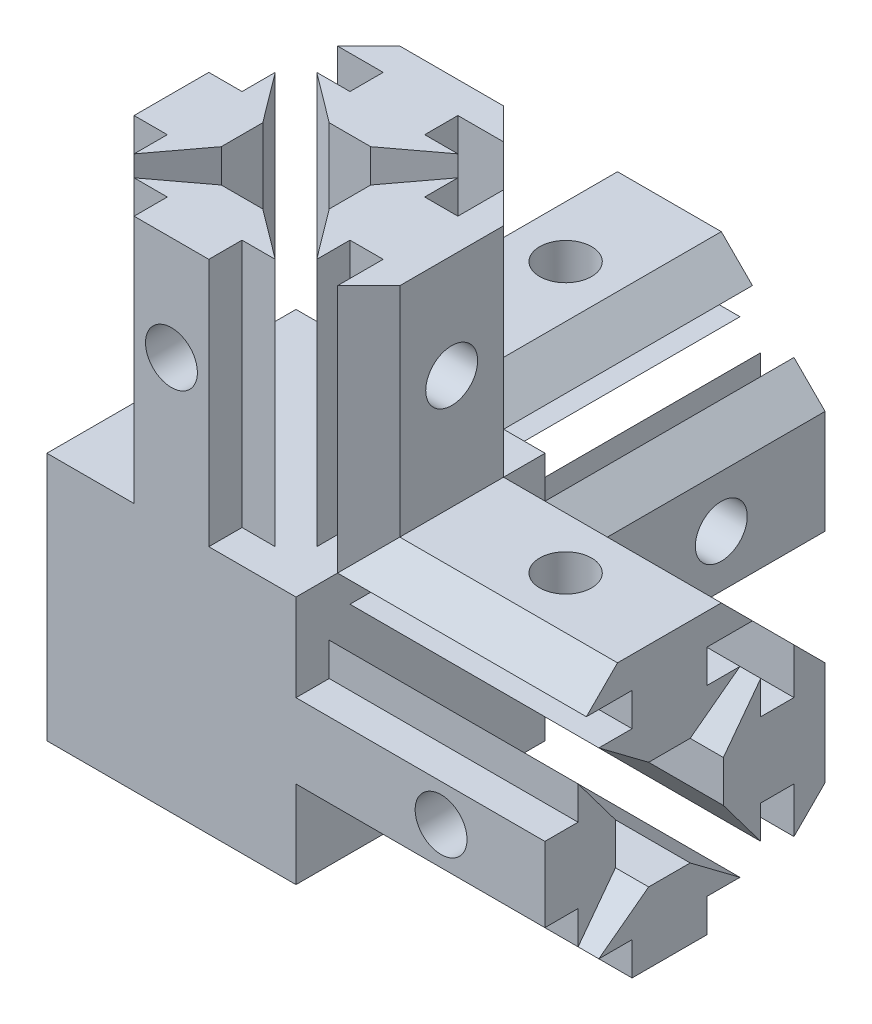
SolidWorks part; units mm, degrees
ref_plane "Plan de face" through (0, 0, 0) normal (0, 0, 1) x (1, 0, 0)
ref_plane "Plan de dessus" through (0, 0, 0) normal (0, 1, 0) x (1, 0, 0)
ref_plane "Plan de droite" through (0, 0, 0) normal (1, 0, 0) x (0, 0, -1)
ref_axis "Axe1" through (0, 17.691, 0) along (0, -1, 0)
ref_axis "Axe2" through (11.6947, 0, 0) along (-1, 0, 0)
ref_axis "Axe3" through (0, 0, -21.7718) along (0, 0, 1)
sketch "Esquisse1" plane through (0, 0, 0) normal (0, 0, 1) x (1, 0, 0)
  line L1 (-6, 6) -> (6, 6)
  line L2 (-6, 6) -> (-6, -6)
  line L3 (-6, -6) -> (6, -6)
  line L4 (6, 6) -> (6, -6)
  point P4 (0, 6)
  point P5 (-6, 0)
  dimension "D1" = 12
  dimension "D2" = 12
extrude "Boss.-Extru.1" add sketch "Esquisse1" along normal mid plane 12
ref_plane "Plan Construction" through (0, 5.99, 0) normal (0, 1, 0) x (1, 0, 0)
sketch "Esquisse8" plane through (0, 5.99, 0) normal (0, 1, 0) x (1, 0, 0)
  line L0 (-6, 1.8) -> (-4.4, 1.8)
  line L2 (-4.4, 1.8) -> (-4.4, 3.4)
  line L3 (-4.4, 3.4) -> (-2.6, 1)
  line L4 (-2.6, 1) -> (-2.6, -1)
  line L5 (-2.6, -1) -> (-4.4, -3.4)
  line L6 (-4.4, -3.4) -> (-4.4, -1.8)
  line L7 (-4.4, -1.8) -> (-6, -1.8)
  line L8 (-6, -1.8) -> (-6, -4)
  line L9 (-6, -4) -> (-7.5, -2.5)
  line L10 (-7.5, -2.5) -> (-7.5, 2.5)
  line L11 (-7.5, 2.5) -> (-6, 4)
  line L12 (-6, 4) -> (-6, 1.8)
  line L13 (11.6947, 0) -> (-10.6939, 0) construction
  line L14 (-6, -6) -> (-6, 6) construction
  point P14 (-2.6, 0)
  dimension "D1" = 1.6
  dimension "D2" = 3.4
  dimension "D3" = 8
  dimension "D4" = 2
  dimension "D5" = 1.6
  dimension "D6" = 45
  dimension "D7" = 1.5
  dimension "D8" = 3.6
extrude "Boss.-Extru.6" add sketch "Esquisse8" along normal blind 12
sketch "Esquisse15" plane through (-2.6, 0, 0) normal (1, 0, 0) x (0, 0, -1)
  line L0 (-1, 17.99) -> (1, 17.99) construction
  circle A0 centre (0, 12.99) radius 1.25
  point P4 (0, 17.99)
  dimension "D1" = 2.5
  dimension "D2" = 5
extrude "Enlèv. mat.-Extru.13" cut sketch "Esquisse15" along normal mid plane 50
pattern_circular "Répétition circulaire10" count 4 every 90 about axis through (0, 17.691, 0) along (0, -1, 0) of "Boss.-Extru.6", "Enlèv. mat.-Extru.13"
pattern_circular "Répétition circulaire11" count 2 every 90 about axis through (11.6947, 0, 0) along (-1, 0, 0) of "Répétition circulaire10"
pattern_circular "Répétition circulaire12" count 2 every 90 about axis through (0, 0, -21.7718) along (0, 0, 1) of "Répétition circulaire10" reverse direction yes
sketch "Esquisse11" plane through (0, 17.99, 0) normal (0, 1, 0) x (1, 0, 0)
  line L1 (-6, -6) -> (-11, -6)
  line L2 (-6, -6) -> (-6, 24)
  line L3 (-6, 24) -> (-11, 24)
  line L4 (-11, -6) -> (-11, 24)
  line L6 (-4, -6) -> (-6, -6) construction
  line L8 (-6, 4) -> (-6, 6) construction
  dimension "D1" = 5
  dimension "D2" = 30
extrude "Enlèv. mat.-Extru.8" cut sketch "Esquisse11" against normal through all
sketch "Esquisse12" plane through (0, 0, -17.99) normal (0, 0, -1) x (-1, 0, 0)
  line L1 (-24, -11) -> (6, -11)
  line L2 (-24, -11) -> (-24, -6)
  line L3 (-24, -6) -> (6, -6)
  line L4 (6, -11) -> (6, -6)
  line L5 (-4, -6) -> (-6, -6) construction
  line L6 (6, -1.8) -> (6, -6) construction
  dimension "D1" = 30
  dimension "D2" = 5
extrude "Enlèv. mat.-Extru.9" cut sketch "Esquisse12" against normal through all
sketch "Esquisse13" plane through (17.99, 0, 0) normal (1, 0, 0) x (0, 0, -1)
  line L0 (-2.5, 17.99) -> (2.5, 17.99) construction
  line L1 (-6, -4) -> (-11, -4)
  line L2 (-6, -4) -> (-6, 17.99)
  line L3 (-6, 17.99) -> (-11, 17.99)
  line L4 (-11, -4) -> (-11, 17.99)
  dimension "D1" = 5
extrude "Enlèv. mat.-Extru.11" cut sketch "Esquisse13" against normal through all
